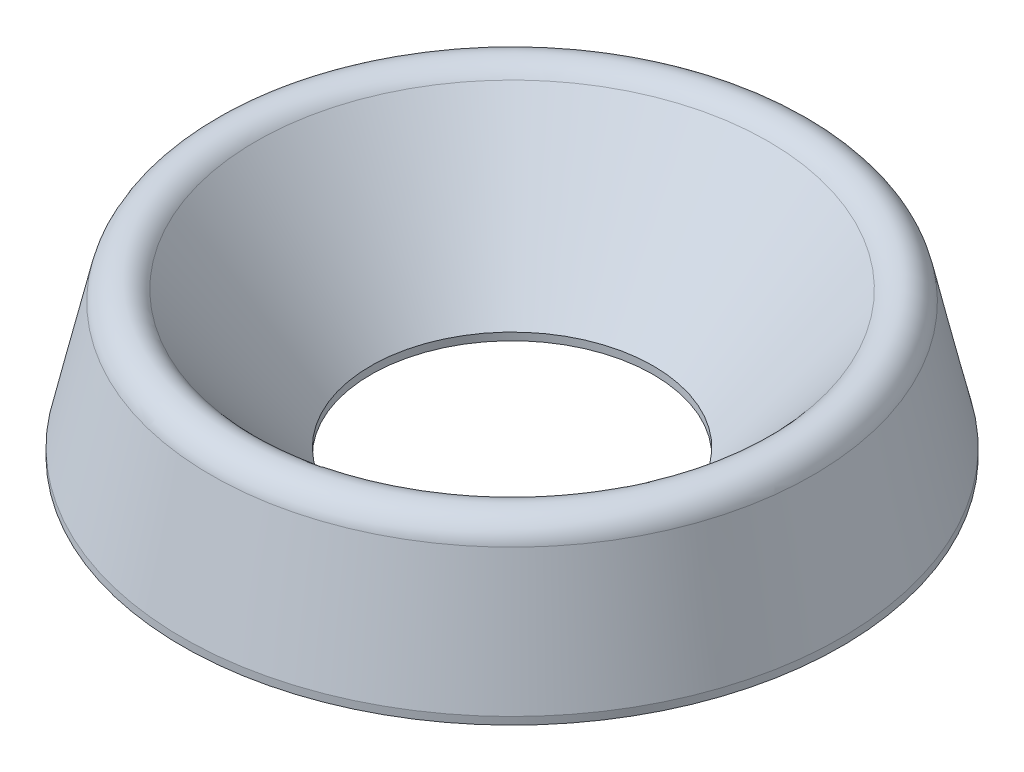
SolidWorks part; units mm, degrees
ref_plane "Front Plane" through (0, 0, 0) normal (0, 0, 1) x (1, 0, 0)
ref_plane "Top Plane" through (0, 0, 0) normal (0, 1, 0) x (1, 0, 0)
ref_plane "Right Plane" through (0, 0, 0) normal (1, 0, 0) x (0, 0, -1)
sketch "Sketch1" plane through (0, 0, 0) normal (0, 0, 1) x (1, 0, 0)
  line L0 (0, 0) -> (0, 3.4451) construction
  line L1 (-2.3813, 0) -> (-2.3813, 3.4451) construction
  line L2 (-5.5562, 0) -> (-5.5562, 0.127)
  line L3 (-5.5562, 0) -> (-5.5562, 3.4451) construction
  line L4 (-2.3813, 0.127) -> (-4.3192, 2.4366)
  line L5 (-2.3813, 0.127) -> (-2.3813, 0)
  line L6 (-2.3813, 0) -> (-5.5562, 0)
  line L7 (-5.5562, 0) -> (-2.3813, 0) construction
  line L8 (-4.65, 0) -> (-4.65, 3.4451) construction
  line L9 (-5.5562, 0.127) -> (-5.071, 2.255)
  arc A0 (-5.071, 2.255) -> (-4.3192, 2.4366) centre (-4.65, 2.159) cw
  arc A1 (5.071, 2.255) -> (4.3192, 2.4366) centre (4.65, 2.159) ccw construction
  dimension "D3" = 0.4318
  dimension "OD" = 11.1125
  dimension "Height" = 2.5908
  dimension "D2" = 40
  dimension "ID" = 4.7625
  dimension "D1" = 0.127
revolve "Revolve1" add sketch "Sketch1" angle 360 about L0
shell "Shell2" thickness 0.7937 removed face at (0, 0, -2.3813)
equation "\"D3@Sketch1\" = \"Height@Sketch1\"/6"
